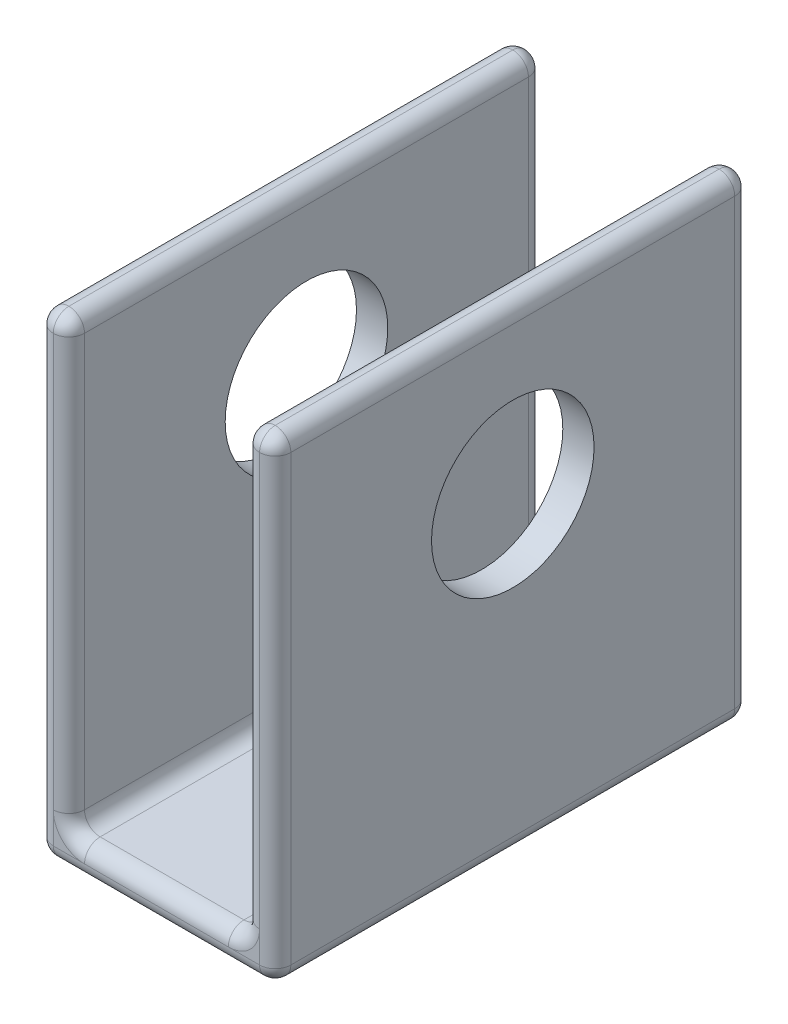
SolidWorks part; units mm, degrees
ref_plane "Front Plane" through (0, 0, 0) normal (0, 0, 1) x (1, 0, 0)
ref_plane "Top Plane" through (0, 0, 0) normal (0, 1, 0) x (1, 0, 0)
ref_plane "Right Plane" through (0, 0, 0) normal (1, 0, 0) x (0, 0, -1)
sketch "Sketch1" plane through (0, 0, 0) normal (0, 0, 1) x (1, 0, 0)
  line L0 (0, 0) -> (0, 17.0397) construction
  line L1 (-9.5, 0) -> (9.5, 0)
  line L2 (9.5, 0) -> (9.5, 38)
  line L3 (-9.5, 0) -> (-9.5, 38)
  line L4 (7, 2.5) -> (7, 36.75)
  line L5 (-7, 2.5) -> (7, 2.5)
  line L6 (-7, 2.5) -> (-7, 36.75)
  line L7 (-9.5, 38) -> (-8.25, 38)
  line L8 (8.25, 38) -> (9.5, 38)
  line L9 (7, 2.5) -> (7, 38) construction
  line L10 (-7, 2.5) -> (-7, 38) construction
  arc A0 (8.25, 38) -> (7, 36.75) centre (8.25, 36.75) ccw
  arc A1 (-8.25, 38) -> (-7, 36.75) centre (-8.25, 36.75) cw
  dimension "D4" = 1.25
  dimension "D1" = 19
  dimension "D2" = 38
  dimension "D3" = 2.5
extrude "Boss-Extrude1" add sketch "Sketch1" along normal blind 38
sketch "Sketch2" plane through (9.5, 0, 0) normal (1, 0, 0) x (0, 0, -1)
  line L0 (-19, 38) -> (-19, 0) construction
  line L1 (-38, 38) -> (0, 38) construction
  line L2 (-38, 0) -> (0, 0) construction
  circle A0 centre (-19, 25) radius 6.5
  dimension "D1" = 13
  dimension "D2" = 13
extrude "Cut-Extrude1" cut sketch "Sketch2" against normal through all
fillet "Fillet1" radius 1.25 22 edges at (-7.3661, 37.6339, 0) (7.3661, 37.6339, 0) (7.3661, 37.6339, 38) (-7.3661, 37.6339, 38) (-9.5, 0, 19) (7, 2.5, 19) (-7, 2.5, 19) (-7, 19.625, 0) (-9.5, 19, 0) (0, 0, 0) (0, 2.5, 0) (7, 19.625, 0) (9.5, 19, 0) (9.5, 0, 19) (0, 0, 38) (-9.5, 19, 38) (-9.5, 38, 19) (9.5, 38, 19) (9.5, 19, 38) (7, 19.625, 38) (-7, 19.625, 38) (0, 2.5, 38)
